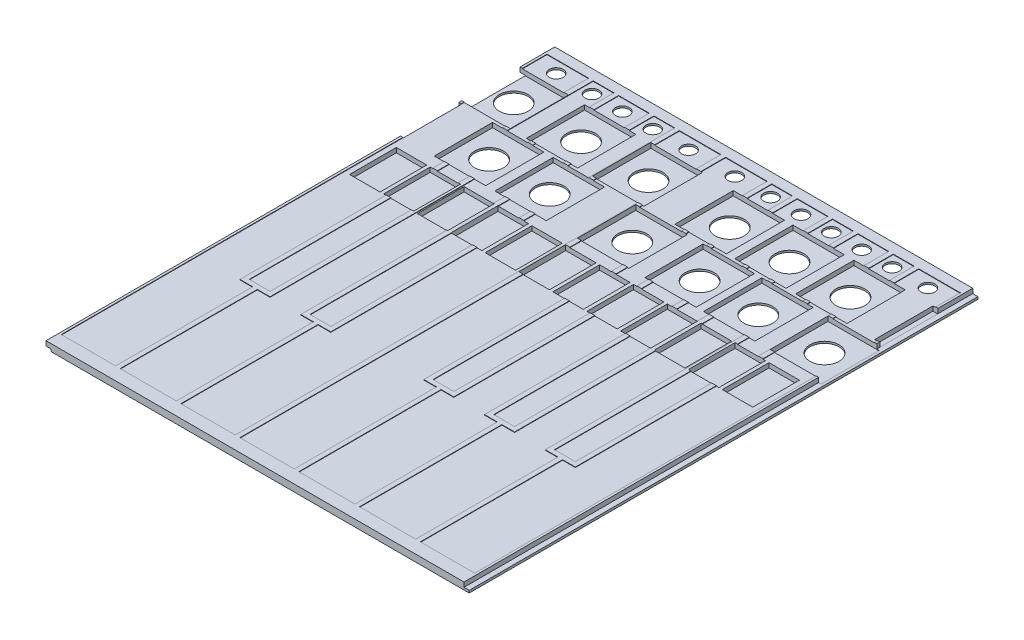
SolidWorks part; units mm, degrees
ref_plane "Plan de face" through (0, 0, 0) normal (0, 0, 1) x (1, 0, 0)
ref_plane "Plan de dessus" through (0, 0, 0) normal (0, 1, 0) x (1, 0, 0)
ref_plane "Plan de droite" through (0, 0, 0) normal (1, 0, 0) x (0, 0, -1)
sketch "Esquisse8" plane through (0, 0, 0) normal (0, 1, 0) x (1, 0, 0)
  line L1 (-19.1004, -13.1969) -> (163.8996, -13.1969)
  line L2 (-19.1004, -13.1969) -> (-19.1004, 206.8031)
  line L3 (-19.1004, 206.8031) -> (163.8996, 206.8031)
  line L4 (163.8996, -13.1969) -> (163.8996, 206.8031)
  dimension "D1" = 183
  dimension "D2" = 220
extrude "Boss.-Extru.2" add sketch "Esquisse8" along normal blind 3 contours L3 L4 L1 L2
sketch "Esquisse12" plane through (0, 3, 0) normal (0, 1, 0) x (1, 0, 0)
  line L0 (163.8996, -13.1969) -> (-19.1004, 206.8031) construction
  line L1 (72.3996, 96.8031) -> (72.0963, 96.8031) construction
  line L2 (12.8796, 130.4409) -> (12.8796, 202.4209)
  line L3 (7.3796, -7.5791) -> (31.6496, -7.5791)
  line L4 (7.3796, 51.6948) -> (12.8796, 51.6948)
  line L5 (7.3796, -7.5791) -> (7.3796, 51.6948)
  line L6 (26.1496, 130.2607) -> (26.1496, 52.2574)
  line L7 (26.1496, 52.2574) -> (26.1496, 51.6948)
  line L8 (26.1496, 51.6948) -> (31.6496, 51.6948)
  line L9 (31.6496, 51.6948) -> (31.6496, -7.5791)
  line L10 (12.8796, 51.6948) -> (12.8796, 130.4409)
  line L11 (12.8796, 202.4209) -> (26.1496, 202.4209)
  line L12 (26.1496, 202.4209) -> (26.1496, 130.2607)
  line L13 (-18.1004, 130.4209) -> (-18.1004, -7.5791)
  line L14 (-18.1004, -7.5791) -> (5.3796, -7.5791)
  line L15 (-0.1204, 130.2607) -> (-0.1204, 52.2574)
  line L16 (-0.1204, 52.2574) -> (-0.1204, 51.6948)
  line L17 (-0.1204, 51.6948) -> (5.3796, 51.6948)
  line L18 (5.3796, 51.6948) -> (5.3796, -7.5791)
  line L19 (1.8796, 131.312) -> (1.8796, 202.4209)
  line L20 (1.8796, 202.4209) -> (10.8796, 202.4209)
  line L21 (10.8796, 202.4209) -> (10.8796, 131.4176)
  line L22 (1.8796, 131.312) -> (1.8796, 53.6948)
  line L23 (1.8796, 53.6948) -> (10.8796, 53.6948)
  line L24 (10.8796, 131.4176) -> (10.8796, 53.6948)
  line L25 (-18.1004, 130.4209) -> (-18.1004, 202.4209)
  line L26 (-18.1004, 202.4209) -> (-0.1204, 202.4209)
  line L27 (-0.1204, 202.4209) -> (-0.1204, 130.2607)
  line L28 (28.1496, 130.2506) -> (28.1496, 202.4209)
  line L29 (28.1496, 202.4209) -> (37.1496, 202.4209)
  line L30 (37.1496, 202.4209) -> (37.1496, 131.4376)
  line L31 (28.1496, 130.2506) -> (28.1496, 53.6948)
  line L32 (28.1496, 53.6948) -> (37.1496, 53.6948)
  line L33 (37.1496, 131.4376) -> (37.1496, 53.6948)
  line L34 (26.1496, 202.4209) -> (30.7258, 202.4209) construction
  line L35 (57.1296, -7.5791) -> (33.6496, -7.5791)
  line L36 (57.1296, 130.4209) -> (57.1296, -7.5791)
  line L37 (39.1496, 129.6999) -> (39.1496, 51.6948)
  line L38 (39.1496, 51.6948) -> (33.6496, 51.6948)
  line L39 (33.6496, 51.6948) -> (33.6496, -7.5791)
  line L40 (39.1496, 129.6999) -> (39.1496, 202.4209)
  line L41 (39.1496, 202.4209) -> (57.1296, 202.4209)
  line L42 (57.1296, 202.4209) -> (57.1296, 130.4209)
  line L43 (59.1296, 130.3659) -> (59.1296, -7.5791)
  line L44 (59.1296, -7.5791) -> (82.6096, -7.5791)
  line L45 (77.1096, 132.5052) -> (77.1096, 54.5019)
  line L46 (77.1096, 54.5019) -> (77.1096, 53.9393)
  line L47 (77.1096, 53.9393) -> (82.6096, 53.9393)
  line L48 (82.6096, 53.9393) -> (82.6096, -7.5791)
  line L49 (59.1296, 130.3659) -> (59.1296, 202.4209)
  line L50 (59.1296, 202.4209) -> (77.1096, 202.4209)
  line L51 (77.1096, 202.4209) -> (77.1096, 132.5052)
  line L52 (-18.1004, -7.5791) -> (-18.1004, -9.5791) construction
  line L53 (-18.1004, 202.4209) -> (-18.1004, 204.4209) construction
  line L54 (-18.1004, 204.4209) -> (128.6652, 204.4209) construction
  line L55 (79.1096, 132.5152) -> (79.1096, 202.4209)
  line L56 (79.1096, 202.4209) -> (88.1096, 202.4209)
  line L57 (88.1096, 202.4209) -> (88.1096, 133.5019)
  line L58 (79.1096, 132.5152) -> (79.1096, 55.9393)
  line L59 (79.1096, 55.9393) -> (88.1096, 55.9393)
  line L60 (88.1096, 133.5019) -> (88.1096, 55.9393)
  line L61 (90.1096, 132.0831) -> (90.1096, 202.4209)
  line L62 (84.6096, -7.5791) -> (108.8796, -7.5791)
  line L63 (84.6096, 53.9393) -> (90.1096, 53.9393)
  line L64 (84.6096, -7.5791) -> (84.6096, 53.9393)
  line L65 (103.3796, 132.5052) -> (103.3796, 54.5019)
  line L66 (103.3796, 54.5019) -> (103.3796, 53.9393)
  line L67 (103.3796, 53.9393) -> (108.8796, 53.9393)
  line L68 (108.8796, 53.9393) -> (108.8796, -7.5791)
  line L69 (90.1096, 53.9393) -> (90.1096, 132.0831)
  line L70 (90.1096, 202.4209) -> (103.3796, 202.4209)
  line L71 (103.3796, 202.4209) -> (103.3796, 132.5052)
  line L72 (105.3796, 132.1219) -> (105.3796, 202.4209)
  line L73 (105.3796, 202.4209) -> (114.3796, 202.4209)
  line L74 (114.3796, 202.4209) -> (114.3796, 132.633)
  line L75 (105.3796, 132.1219) -> (105.3796, 55.9393)
  line L76 (105.3796, 55.9393) -> (114.3796, 55.9393)
  line L77 (114.3796, 132.633) -> (114.3796, 55.9393)
  line L78 (116.3796, 132.5052) -> (116.3796, 202.4209)
  line L79 (110.8796, -7.5791) -> (135.1496, -7.5791)
  line L80 (110.8796, 53.9393) -> (116.3796, 53.9393)
  line L81 (110.8796, -7.5791) -> (110.8796, 53.9393)
  line L82 (129.6496, 132.5052) -> (129.6496, 54.5019)
  line L83 (129.6496, 54.5019) -> (129.6496, 53.9393)
  line L84 (129.6496, 53.9393) -> (135.1496, 53.9393)
  line L85 (135.1496, 53.9393) -> (135.1496, -7.5791)
  line L86 (116.3796, 53.9393) -> (116.3796, 132.5052)
  line L87 (116.3796, 202.4209) -> (129.6496, 202.4209)
  line L88 (129.6496, 202.4209) -> (129.6496, 132.5052)
  line L89 (131.6496, 133.2845) -> (131.6496, 202.4209)
  line L90 (131.6496, 202.4209) -> (140.6496, 202.4209)
  line L91 (140.6496, 202.4209) -> (140.6496, 133.5019)
  line L92 (131.6496, 133.2845) -> (131.6496, 55.9393)
  line L93 (131.6496, 55.9393) -> (140.6496, 55.9393)
  line L94 (140.6496, 133.5019) -> (140.6496, 55.9393)
  line L95 (160.6296, -7.5791) -> (137.1496, -7.5791)
  line L96 (160.6296, 130.4209) -> (160.6296, -7.5791)
  line L97 (142.6496, 131.9444) -> (142.6496, 53.9393)
  line L98 (142.6496, 53.9393) -> (137.1496, 53.9393)
  line L99 (137.1496, 53.9393) -> (137.1496, -7.5791)
  line L100 (142.6496, 131.9444) -> (142.6496, 202.4209)
  line L101 (142.6496, 202.4209) -> (160.6296, 202.4209)
  line L102 (160.6296, 202.4209) -> (160.6296, 130.4209)
  line L103 (5.3796, 51.6948) -> (7.3796, 51.6948) construction
  line L104 (-0.1204, 53.129) -> (12.8796, 53.129) construction
  line L105 (-19.1004, -13.1969) -> (-19.1004, 206.8031) construction
  point P56 (68.1196, 202.4209)
  dimension "D4" = 2
  dimension "D5" = 2
  dimension "D6" = 2
  dimension "D7" = 2
  dimension "D8" = 2
  dimension "D9" = 2
  dimension "D10" = 2
  dimension "D11" = 2
  dimension "D12" = 2
  dimension "D13" = 2
  dimension "D14" = 2
  dimension "D15" = 2
  dimension "D16" = 2
  dimension "D17" = 2
  dimension "D18" = 2
  dimension "D19" = 2
  dimension "D20" = 2
  dimension "D21" = 2
  dimension "D22" = 2
  dimension "D23" = 2
  dimension "D24" = 2
  dimension "D25" = 2
  dimension "D26" = 2
  dimension "D27" = 2
  dimension "D28" = 2
  dimension "D29" = 2
  dimension "D30" = 2
  dimension "D31" = 5.5
  dimension "D32" = 2
  dimension "D33" = 5.5
  dimension "D34" = 5.5
  dimension "D35" = 5.5
  dimension "D36" = 5.5
  dimension "D37" = 5.5
  dimension "D38" = 5.5
  dimension "D39" = 5.5
  dimension "D40" = 2
  dimension "D41" = 2
  dimension "D42" = 2
  dimension "D43" = 5.5
  dimension "D44" = 5.5
  dimension "D45" = 2
  dimension "D46" = 2
  dimension "D47" = 2
  dimension "D48" = 2
  dimension "D49" = 2
  dimension "D50" = 210
  dimension "D51" = 210
  dimension "D52" = 210
  dimension "D53" = 210
  dimension "D54" = 210
  dimension "D55" = 210
  dimension "D56" = 210
  dimension "D57" = 17.98
  dimension "D58" = 13.27
  dimension "D59" = 13.27
  dimension "D60" = 17.98
  dimension "D61" = 17.98
  dimension "D62" = 13.27
  dimension "D63" = 17.98
  dimension "D64" = 2
  dimension "D65" = 2
  dimension "D66" = 1
extrude "Enlèv. mat.-Extru.8" cut sketch "Esquisse12" against normal blind 0.2
sketch "Esquisse14" plane through (0, 2.8, 0) normal (0, 1, 0) x (1, 0, 0)
  line L0 (-9.1104, 202.4209) -> (-9.1104, 197.4209) construction
  line L1 (-0.1204, 202.4209) -> (-18.1004, 202.4209) construction
  line L2 (-9.1104, 197.4209) -> (162.3729, 197.4209) construction
  line L3 (6.3796, 202.4209) -> (6.3796, 197.4209) construction
  line L4 (10.8796, 202.4209) -> (1.8796, 202.4209) construction
  line L5 (19.5146, 202.4209) -> (19.5146, 197.4209) construction
  line L6 (26.1496, 202.4209) -> (12.8796, 202.4209) construction
  line L7 (32.6496, 202.4209) -> (32.6496, 197.4209) construction
  line L8 (37.1496, 202.4209) -> (28.1496, 202.4209) construction
  line L9 (48.1396, 202.4209) -> (48.1396, 197.4209) construction
  line L10 (57.1296, 202.4209) -> (39.1496, 202.4209) construction
  line L11 (68.1196, 202.4209) -> (68.1196, 197.4209) construction
  line L12 (77.1096, 202.4209) -> (59.1296, 202.4209) construction
  line L13 (83.6096, 202.4209) -> (83.6096, 197.4209) construction
  line L14 (88.1096, 202.4209) -> (79.1096, 202.4209) construction
  line L15 (96.7446, 202.4209) -> (96.7446, 197.4209) construction
  line L16 (103.3796, 202.4209) -> (90.1096, 202.4209) construction
  line L17 (109.8796, 202.4209) -> (109.8796, 197.4209) construction
  line L18 (114.3796, 202.4209) -> (105.3796, 202.4209) construction
  line L19 (123.0146, 202.4209) -> (123.0146, 197.4209) construction
  line L20 (129.6496, 202.4209) -> (116.3796, 202.4209) construction
  line L21 (136.1496, 202.4209) -> (136.1496, 197.4209) construction
  line L22 (140.6496, 202.4209) -> (131.6496, 202.4209) construction
  line L23 (151.6396, 202.4209) -> (151.6396, 197.4209) construction
  line L24 (160.6296, 202.4209) -> (142.6496, 202.4209) construction
  circle A0 centre (-9.1104, 197.4209) radius 3
  circle A1 centre (6.3796, 197.4209) radius 3
  circle A2 centre (19.5146, 197.4209) radius 3
  circle A3 centre (32.6496, 197.4209) radius 3
  circle A4 centre (48.1396, 197.4209) radius 3
  circle A5 centre (68.1196, 197.4209) radius 3
  circle A6 centre (83.6096, 197.4209) radius 3
  circle A7 centre (96.7446, 197.4209) radius 3
  circle A8 centre (109.8796, 197.4209) radius 3
  circle A9 centre (123.0146, 197.4209) radius 3
  circle A10 centre (136.1496, 197.4209) radius 3
  circle A11 centre (151.6396, 197.4209) radius 3
extrude "Enlèv. mat.-Extru.9" cut sketch "Esquisse14" against normal blind 10
sketch "Esquisse15" plane through (0, 2.8, 0) normal (0, 1, 0) x (1, 0, 0)
  line L0 (-19.1004, 206.8031) -> (163.8996, 206.8031) construction
  line L6 (-4.5051, 165.3031) -> (17.6949, 165.3031)
  line L7 (-20.341, 191.8031) -> (1.859, 191.8031)
  line L8 (-20.341, 191.8031) -> (-20.341, 166.6031)
  line L9 (-20.341, 166.6031) -> (1.859, 166.6031)
  line L10 (1.859, 191.8031) -> (1.859, 166.6031)
  line L11 (-4.5051, 165.3031) -> (-4.5051, 140.1031)
  line L12 (-4.5051, 140.1031) -> (17.6949, 140.1031)
  line L13 (17.6949, 165.3031) -> (17.6949, 140.1031)
  line L14 (8.7728, 191.8031) -> (30.9728, 191.8031)
  line L15 (8.7728, 191.8031) -> (8.7728, 166.6031)
  line L16 (8.7728, 166.6031) -> (30.9728, 166.6031)
  line L17 (30.9728, 191.8031) -> (30.9728, 166.6031)
  line L18 (21.6997, 165.3031) -> (43.8997, 165.3031)
  line L19 (21.6997, 165.3031) -> (21.6997, 140.1031)
  line L20 (21.6997, 140.1031) -> (43.8997, 140.1031)
  line L21 (43.8997, 165.3031) -> (43.8997, 140.1031)
  line L22 (37.4261, 191.8031) -> (59.6261, 191.8031)
  line L23 (37.4261, 191.8031) -> (37.4261, 166.6031)
  line L24 (37.4261, 166.6031) -> (59.6261, 166.6031)
  line L25 (59.6261, 191.8031) -> (59.6261, 166.6031)
  line L26 (57.4227, 165.3031) -> (79.6227, 165.3031)
  line L27 (57.4227, 165.3031) -> (57.4227, 140.1031)
  line L28 (57.4227, 140.1031) -> (79.6227, 140.1031)
  line L29 (79.6227, 165.3031) -> (79.6227, 140.1031)
  line L30 (73.063, 191.8031) -> (95.263, 191.8031)
  line L31 (73.063, 191.8031) -> (73.063, 166.6031)
  line L32 (73.063, 166.6031) -> (95.263, 166.6031)
  line L33 (95.263, 191.8031) -> (95.263, 166.6031)
  line L34 (86.5318, 165.3031) -> (108.7318, 165.3031)
  line L35 (86.5318, 165.3031) -> (86.5318, 140.1031)
  line L36 (86.5318, 140.1031) -> (108.7318, 140.1031)
  line L37 (108.7318, 165.3031) -> (108.7318, 140.1031)
  line L38 (98.8805, 191.8031) -> (121.0805, 191.8031)
  line L39 (98.8805, 191.8031) -> (98.8805, 166.6031)
  line L40 (98.8805, 166.6031) -> (121.0805, 166.6031)
  line L41 (121.0805, 191.8031) -> (121.0805, 166.6031)
  line L42 (111.9109, 165.3031) -> (134.1109, 165.3031)
  line L43 (111.9109, 165.3031) -> (111.9109, 140.1031)
  line L44 (111.9109, 140.1031) -> (134.1109, 140.1031)
  line L45 (134.1109, 165.3031) -> (134.1109, 140.1031)
  line L46 (125.2379, 191.8031) -> (147.4379, 191.8031)
  line L47 (125.2379, 191.8031) -> (125.2379, 166.6031)
  line L48 (125.2379, 166.6031) -> (147.4379, 166.6031)
  line L49 (147.4379, 191.8031) -> (147.4379, 166.6031)
  line L50 (140.5398, 165.3031) -> (162.7398, 165.3031)
  line L51 (140.5398, 165.3031) -> (140.5398, 140.1031)
  line L52 (140.5398, 140.1031) -> (162.7398, 140.1031)
  line L53 (162.7398, 165.3031) -> (162.7398, 140.1031)
  line L54 (-19.1004, 191.8031) -> (190.2079, 191.8031) construction
  line L55 (-19.1004, -13.1969) -> (-19.1004, 206.8031) construction
  line L56 (-19.1004, 165.5149) -> (203.3844, 166.3385) construction
  dimension "D1" = 15
  dimension "D2" = 15
  dimension "D3" = 22.2
  dimension "D4" = 25.2
  dimension "D5" = 15
  dimension "D6" = 15
  dimension "D7" = 15
  dimension "D8" = 15
  dimension "D9" = 15
  dimension "D10" = 0.212
  dimension "D11" = 41.5
  dimension "D12" = 41.5
  dimension "D13" = 41.5
  dimension "D14" = 41.5
  dimension "D15" = 41.5
  dimension "D16" = 41.5
  dimension "D17" = 25.2
  dimension "D18" = 25.2
  dimension "D19" = 25.2
  dimension "D20" = 25.2
  dimension "D21" = 25.2
  dimension "D22" = 22.2
  dimension "D23" = 22.2
  dimension "D24" = 22.2
  dimension "D25" = 22.2
  dimension "D26" = 22.2
  dimension "D27" = 22.2
  dimension "D28" = 22.2
  dimension "D29" = 22.2
  dimension "D30" = 22.2
  dimension "D31" = 22.2
  dimension "D32" = 22.2
  dimension "D33" = 25.2
  dimension "D34" = 25.2
  dimension "D35" = 25.2
  dimension "D36" = 25.2
  dimension "D37" = 25.2
  dimension "D38" = 25.2
extrude "Enlèv. mat.-Extru.10" cut sketch "Esquisse15" against normal blind 2 and the other way blind 2
sketch "Esquisse16" plane through (0, 0.8, 0) normal (0, 1, 0) x (1, 0, 0)
  line L0 (-20.341, 191.8031) -> (1.859, 166.6031) construction
  line L1 (-4.5051, 165.3031) -> (17.6949, 140.1031) construction
  line L2 (8.7728, 166.6031) -> (30.9728, 191.8031) construction
  line L3 (43.8997, 165.3031) -> (21.6997, 140.1031) construction
  line L5 (57.4227, 140.1031) -> (79.6227, 165.3031) construction
  line L6 (1.859, 191.8031) -> (-20.341, 191.8031) construction
  line L7 (73.063, 191.8031) -> (95.263, 166.6031) construction
  line L8 (98.8805, 191.8031) -> (121.0805, 166.6031) construction
  line L9 (86.5318, 165.3031) -> (108.7318, 140.1031) construction
  line L10 (125.2379, 191.8031) -> (147.4379, 166.6031) construction
  line L11 (111.9109, 165.3031) -> (134.1109, 140.1031) construction
  line L12 (140.5398, 165.3031) -> (162.7398, 140.1031) construction
  circle A1 centre (19.8728, 179.2031) radius 6.25
  circle A2 centre (49.0329, 179.2031) radius 6.25
  circle A3 centre (84.163, 179.2031) radius 6.25
  circle A4 centre (109.9805, 179.2031) radius 6.25
  circle A5 centre (136.3379, 179.2031) radius 6.25
  circle A6 centre (6.5949, 152.7031) radius 6.25
  circle A7 centre (32.7997, 152.7031) radius 6.25
  circle A8 centre (68.5227, 152.7031) radius 6.25
  circle A9 centre (97.6318, 152.7031) radius 6.25
  circle A10 centre (123.0109, 152.7031) radius 6.25
  circle A11 centre (151.6398, 152.7031) radius 6.25
  circle A12 centre (-9.241, 179.2031) radius 6.25
extrude "Enlèv. mat.-Extru.11" cut sketch "Esquisse16" against normal blind 2 contours A1 | A6 | A7 | A2 | A8 | A3 | A9 | A4 | A10 | A5 | A11 | A12 region at (19.8728, 0.8, -179.2031) region at (49.0329, 0.8, -179.2031) region at (84.163, 0.8, -179.2031) region at (109.9805, 0.8, -179.2031) region at (136.3379, 0.8, -179.2031) region at (6.5949, 0.8, -152.7031) region at (32.7997, 0.8, -152.7031) region at (68.5227, 0.8, -152.7031) region at (97.6318, 0.8, -152.7031) region at (123.0109, 0.8, -152.7031) region at (151.6398, 0.8, -152.7031)
sketch "Esquisse21" plane through (0, 0, 0) normal (0, -1, 0) x (-1, 0, 0)
  line L1 (14.1104, 192.4209) -> (4.1104, 192.4209)
  line L2 (14.1104, 192.4209) -> (14.1104, 202.4209)
  line L3 (14.1104, 202.4209) -> (4.1104, 202.4209)
  line L4 (4.1104, 192.4209) -> (4.1104, 202.4209)
  line L5 (14.1104, 192.4209) -> (4.1104, 202.4209) construction
  line L6 (14.1104, 202.4209) -> (4.1104, 192.4209) construction
  line L7 (-1.3796, 192.4209) -> (-11.3796, 192.4209)
  line L8 (-1.3796, 192.4209) -> (-1.3796, 202.4209)
  line L9 (-1.3796, 202.4209) -> (-11.3796, 202.4209)
  line L10 (-11.3796, 192.4209) -> (-11.3796, 202.4209)
  line L11 (-1.3796, 192.4209) -> (-11.3796, 202.4209) construction
  line L12 (-1.3796, 202.4209) -> (-11.3796, 192.4209) construction
  line L13 (-14.5146, 192.4209) -> (-24.5146, 192.4209)
  line L14 (-14.5146, 192.4209) -> (-14.5146, 202.4209)
  line L15 (-14.5146, 202.4209) -> (-24.5146, 202.4209)
  line L16 (-24.5146, 192.4209) -> (-24.5146, 202.4209)
  line L17 (-14.5146, 192.4209) -> (-24.5146, 202.4209) construction
  line L18 (-14.5146, 202.4209) -> (-24.5146, 192.4209) construction
  line L19 (-27.6496, 192.4209) -> (-37.6496, 192.4209)
  line L20 (-27.6496, 192.4209) -> (-27.6496, 202.4209)
  line L21 (-27.6496, 202.4209) -> (-37.6496, 202.4209)
  line L22 (-37.6496, 192.4209) -> (-37.6496, 202.4209)
  line L23 (-27.6496, 192.4209) -> (-37.6496, 202.4209) construction
  line L24 (-27.6496, 202.4209) -> (-37.6496, 192.4209) construction
  line L25 (-43.1396, 192.4209) -> (-53.1396, 192.4209)
  line L26 (-43.1396, 192.4209) -> (-43.1396, 202.4209)
  line L27 (-43.1396, 202.4209) -> (-53.1396, 202.4209)
  line L28 (-53.1396, 192.4209) -> (-53.1396, 202.4209)
  line L29 (-43.1396, 192.4209) -> (-53.1396, 202.4209) construction
  line L30 (-43.1396, 202.4209) -> (-53.1396, 192.4209) construction
  line L31 (-63.1196, 192.4209) -> (-73.1196, 192.4209)
  line L32 (-63.1196, 192.4209) -> (-63.1196, 202.4209)
  line L33 (-63.1196, 202.4209) -> (-73.1196, 202.4209)
  line L34 (-73.1196, 192.4209) -> (-73.1196, 202.4209)
  line L35 (-63.1196, 192.4209) -> (-73.1196, 202.4209) construction
  line L36 (-63.1196, 202.4209) -> (-73.1196, 192.4209) construction
  line L37 (-78.6096, 192.4209) -> (-88.6096, 192.4209)
  line L38 (-78.6096, 192.4209) -> (-78.6096, 202.4209)
  line L39 (-78.6096, 202.4209) -> (-88.6096, 202.4209)
  line L40 (-88.6096, 192.4209) -> (-88.6096, 202.4209)
  line L41 (-78.6096, 192.4209) -> (-88.6096, 202.4209) construction
  line L42 (-78.6096, 202.4209) -> (-88.6096, 192.4209) construction
  line L43 (-91.7446, 192.4209) -> (-101.7446, 192.4209)
  line L44 (-91.7446, 192.4209) -> (-91.7446, 202.4209)
  line L45 (-91.7446, 202.4209) -> (-101.7446, 202.4209)
  line L46 (-101.7446, 192.4209) -> (-101.7446, 202.4209)
  line L47 (-91.7446, 192.4209) -> (-101.7446, 202.4209) construction
  line L48 (-91.7446, 202.4209) -> (-101.7446, 192.4209) construction
  line L49 (-104.8796, 192.4209) -> (-114.8796, 192.4209)
  line L50 (-104.8796, 192.4209) -> (-104.8796, 202.4209)
  line L51 (-104.8796, 202.4209) -> (-114.8796, 202.4209)
  line L52 (-114.8796, 192.4209) -> (-114.8796, 202.4209)
  line L53 (-104.8796, 192.4209) -> (-114.8796, 202.4209) construction
  line L54 (-104.8796, 202.4209) -> (-114.8796, 192.4209) construction
  line L55 (-118.0146, 192.4209) -> (-128.0146, 192.4209)
  line L56 (-118.0146, 192.4209) -> (-118.0146, 202.4209)
  line L57 (-118.0146, 202.4209) -> (-128.0146, 202.4209)
  line L58 (-128.0146, 192.4209) -> (-128.0146, 202.4209)
  line L59 (-118.0146, 192.4209) -> (-128.0146, 202.4209) construction
  line L60 (-118.0146, 202.4209) -> (-128.0146, 192.4209) construction
  line L61 (-131.1496, 192.4209) -> (-141.1496, 192.4209)
  line L62 (-131.1496, 192.4209) -> (-131.1496, 202.4209)
  line L63 (-131.1496, 202.4209) -> (-141.1496, 202.4209)
  line L64 (-141.1496, 192.4209) -> (-141.1496, 202.4209)
  line L65 (-131.1496, 192.4209) -> (-141.1496, 202.4209) construction
  line L66 (-131.1496, 202.4209) -> (-141.1496, 192.4209) construction
  line L67 (-146.6396, 192.4209) -> (-156.6396, 192.4209)
  line L68 (-146.6396, 192.4209) -> (-146.6396, 202.4209)
  line L69 (-146.6396, 202.4209) -> (-156.6396, 202.4209)
  line L70 (-156.6396, 192.4209) -> (-156.6396, 202.4209)
  line L71 (-146.6396, 192.4209) -> (-156.6396, 202.4209) construction
  line L72 (-146.6396, 202.4209) -> (-156.6396, 192.4209) construction
  point P0 (9.1104, 197.4209)
  point P6 (-6.3796, 197.4209)
  point P12 (-19.5146, 197.4209)
  point P18 (-32.6496, 197.4209)
  point P24 (-48.1396, 197.4209)
  point P30 (-68.1196, 197.4209)
  point P36 (-83.6096, 197.4209)
  point P42 (-96.7446, 197.4209)
  point P48 (-109.8796, 197.4209)
  point P54 (-123.0146, 197.4209)
  point P60 (-136.1496, 197.4209)
  point P66 (-151.6396, 197.4209)
extrude "Enlèv. mat.-Extru.16" cut sketch "Esquisse21" against normal blind 2
sketch "Esquisse22" plane through (0, 3, 0) normal (0, 1, 0) x (1, 0, 0)
  line L0 (160.6296, 200.1746) -> (156.3183, 200.1746) construction
  line L1 (160.6296, 165.3031) -> (160.6296, 202.4209) construction
  line L2 (-19.1004, 206.8031) -> (163.8996, 206.8031) construction
  line L3 (161.6296, 206.8031) -> (163.8996, 206.8031)
  line L4 (161.6296, 206.8031) -> (161.6296, -13.1969)
  line L5 (161.6296, -13.1969) -> (163.8996, -13.1969)
  line L6 (163.8996, 206.8031) -> (163.8996, -13.1969)
  dimension "D1" = 1
extrude "Enlèv. mat.-Extru.17" cut sketch "Esquisse22" against normal blind 2 contours L4 L5 L6 L3
sketch "Esquisse24" plane through (0, 0.8, 0) normal (0, 1, 0) x (1, 0, 0)
  line L1 (162.7398, 165.3031) -> (161.6296, 165.3031)
  line L2 (162.7398, 165.3031) -> (162.7398, 140.1031)
  line L3 (162.7398, 140.1031) -> (161.6296, 140.1031)
  line L4 (161.6296, 165.3031) -> (161.6296, 140.1031)
  line L5 (-19.1004, 209.6913) -> (161.6296, 209.6913) construction
  line L7 (71.2646, 206.8031) -> (70.2646, 206.8031) construction
  line L9 (-19.1004, 206.8031) -> (161.6296, 206.8031) construction
  line L10 (71.2646, 206.8031) -> (71.8197, 206.8031) construction
  line L11 (71.8197, 206.8031) -> (71.8197, -69.8958) construction
  line L12 (-19.1003, 140.1031) -> (-17.9902, 140.1031)
  line L13 (-17.9902, 165.3031) -> (-17.9902, 140.1031)
  line L14 (-19.1003, 165.3031) -> (-17.9902, 165.3031)
  line L15 (-19.1003, 165.3031) -> (-19.1003, 140.1031)
extrude "Enlèv. mat.-Extru.18" cut sketch "Esquisse24" against normal blind 1 and the other way blind 8 contours L14 L13 L12 L15
sketch "Esquisse25" plane through (-17.9902, 0, 0) normal (-1, 0, 0) x (0, 0, 1)
  line L0 (-140.1031, 2.8) -> (-140.1031, 0) construction
  line L1 (-165.3031, 0) -> (-140.1031, 0)
  line L2 (-165.3031, 0) -> (-165.3031, 0.8)
  line L3 (-165.3031, 0.8) -> (-140.1031, 0.8)
  line L4 (-140.1031, 0) -> (-140.1031, 0.8)
  line L5 (-166.6031, 0.8) -> (-191.8031, 0.8) construction
  line L6 (-165.3031, 0) -> (-206.8031, 0) construction
  dimension "D1" = 0.8
  dimension "D2" = 0.8
extrude "Boss.-Extru.3" add sketch "Esquisse25" along normal blind 1.11 contours L3 L4 L1 L2
sketch "Esquisse26" plane through (0, 2.8, 0) normal (0, 1, 0) x (1, 0, 0)
  line L0 (161.6296, 206.8031) -> (161.6296, 165.3031) construction
  line L1 (159.4296, 191.8031) -> (161.6296, 191.8031)
  line L2 (159.4296, 191.8031) -> (159.4296, 166.6031)
  line L3 (159.4296, 166.6031) -> (161.6296, 166.6031)
  line L4 (161.6296, 191.8031) -> (161.6296, 166.6031)
  line L6 (-19.1004, 206.8031) -> (161.6296, 206.8031) construction
  dimension "D1" = 2.2
  dimension "D2" = 25.2
  dimension "D3" = 15
extrude "Enlèv. mat.-Extru.19" cut sketch "Esquisse26" against normal blind 2 and the other way blind 2
sketch "Esquisse27" plane through (0, 2.8, 0) normal (0, 1, 0) x (1, 0, 0)
  line L0 (-19.1003, 140.1031) -> (163.8996, 140.1031) construction
  line L1 (163.8996, 206.8031) -> (163.8996, -13.1969) construction
  line L2 (-1.2716, 135.1031) -> (11.8784, 135.1031)
  line L3 (-15.9216, 135.1031) -> (-2.7716, 135.1031)
  line L4 (-15.9216, 135.1031) -> (-15.9216, 114.9031)
  line L5 (-15.9216, 114.9031) -> (-2.7716, 114.9031)
  line L6 (-2.7716, 135.1031) -> (-2.7716, 114.9031)
  line L7 (-1.2716, 135.1031) -> (-1.2716, 114.9031)
  line L8 (-1.2716, 114.9031) -> (11.8784, 114.9031)
  line L9 (11.8784, 135.1031) -> (11.8784, 114.9031)
  line L10 (-9.5142, 10.1) -> (3.6358, 10.1)
  line L11 (-9.5142, 10.1) -> (-9.5142, -10.1)
  line L12 (-9.5142, -10.1) -> (3.6358, -10.1)
  line L13 (3.6358, 10.1) -> (3.6358, -10.1)
  line L14 (-2.9392, 10.1) -> (10.2108, 10.1)
  line L15 (-2.9392, 10.1) -> (-2.9392, -10.1)
  line L16 (-2.9392, -10.1) -> (10.2108, -10.1)
  line L17 (10.2108, 10.1) -> (10.2108, -10.1)
  line L22 (-8.1813, -52.5449) -> (4.9687, -52.5449)
  line L23 (-8.1813, -52.5449) -> (-8.1813, -72.7449)
  line L24 (-8.1813, -72.7449) -> (4.9687, -72.7449)
  line L25 (4.9687, -52.5449) -> (4.9687, -72.7449)
  line L26 (13.3784, 135.1031) -> (26.5284, 135.1031)
  line L27 (13.3784, 135.1031) -> (13.3784, 114.9031)
  line L28 (13.3784, 114.9031) -> (26.5284, 114.9031)
  line L29 (26.5284, 135.1031) -> (26.5284, 114.9031)
  line L30 (28.0284, 135.1465) -> (41.1784, 135.1465)
  line L31 (28.0284, 135.1465) -> (28.0284, 114.9465)
  line L32 (28.0284, 114.9465) -> (41.1784, 114.9465)
  line L33 (41.1784, 135.1465) -> (41.1784, 114.9465)
  line L34 (18.9541, 10.1) -> (32.1041, 10.1)
  line L35 (18.9541, 10.1) -> (18.9541, -10.1)
  line L36 (18.9541, -10.1) -> (32.1041, -10.1)
  line L37 (32.1041, 10.1) -> (32.1041, -10.1)
  line L38 (42.6784, 135.1031) -> (55.8284, 135.1031)
  line L39 (42.6784, 135.1031) -> (42.6784, 114.9031)
  line L40 (42.6784, 114.9031) -> (55.8284, 114.9031)
  line L41 (55.8284, 135.1031) -> (55.8284, 114.9031)
  line L42 (49.2879, 10.1) -> (62.4379, 10.1)
  line L43 (49.2879, 10.1) -> (49.2879, -10.1)
  line L44 (49.2879, -10.1) -> (62.4379, -10.1)
  line L45 (62.4379, 10.1) -> (62.4379, -10.1)
  line L46 (57.3284, 135.1031) -> (70.4784, 135.1031)
  line L47 (57.3284, 135.1031) -> (57.3284, 114.9031)
  line L48 (57.3284, 114.9031) -> (70.4784, 114.9031)
  line L49 (70.4784, 135.1031) -> (70.4784, 114.9031)
  line L50 (62.9949, 10.1) -> (76.1449, 10.1)
  line L51 (62.9949, 10.1) -> (62.9949, -10.1)
  line L52 (62.9949, -10.1) -> (76.1449, -10.1)
  line L53 (76.1449, 10.1) -> (76.1449, -10.1)
  line L54 (71.9784, 135.1031) -> (85.1284, 135.1031)
  line L55 (71.9784, 135.1031) -> (71.9784, 114.9031)
  line L56 (71.9784, 114.9031) -> (85.1284, 114.9031)
  line L57 (85.1284, 135.1031) -> (85.1284, 114.9031)
  line L58 (86.6284, 135.1031) -> (99.7784, 135.1031)
  line L59 (86.6284, 135.1031) -> (86.6284, 114.9031)
  line L60 (86.6284, 114.9031) -> (99.7784, 114.9031)
  line L61 (99.7784, 135.1031) -> (99.7784, 114.9031)
  line L62 (101.2784, 135.1031) -> (114.4284, 135.1031)
  line L63 (101.2784, 135.1031) -> (101.2784, 114.9031)
  line L64 (101.2784, 114.9031) -> (114.4284, 114.9031)
  line L65 (114.4284, 135.1031) -> (114.4284, 114.9031)
  line L66 (115.9284, 135.1031) -> (129.0784, 135.1031)
  line L67 (115.9284, 135.1031) -> (115.9284, 114.9031)
  line L68 (115.9284, 114.9031) -> (129.0784, 114.9031)
  line L69 (129.0784, 135.1031) -> (129.0784, 114.9031)
  line L70 (130.5784, 135.1031) -> (143.7284, 135.1031)
  line L71 (130.5784, 135.1031) -> (130.5784, 114.9031)
  line L72 (130.5784, 114.9031) -> (143.7284, 114.9031)
  line L73 (143.7284, 135.1031) -> (143.7284, 114.9031)
  line L74 (145.2284, 135.1031) -> (158.3784, 135.1031)
  line L75 (145.2284, 135.1031) -> (145.2284, 114.9031)
  line L76 (145.2284, 114.9031) -> (158.3784, 114.9031)
  line L77 (158.3784, 135.1031) -> (158.3784, 114.9031)
  dimension "D1" = 5
  dimension "D2" = 5
  dimension "D3" = 5
  dimension "D4" = 5
  dimension "D5" = 5
  dimension "D6" = 5
  dimension "D7" = 5
  dimension "D8" = 5
  dimension "D9" = 5
  dimension "D10" = 5
  dimension "D11" = 5
  dimension "D12" = 1.5
  dimension "D13" = 1.5
  dimension "D14" = 1.5
  dimension "D15" = 1.5
  dimension "D16" = 1.5
  dimension "D17" = 1.5
  dimension "D18" = 1.5
  dimension "D19" = 1.5
  dimension "D20" = 1.5
  dimension "D21" = 1.5
  dimension "D22" = 1.5
extrude "Enlèv. mat.-Extru.20" cut sketch "Esquisse27" against normal blind 2 and the other way blind 2 contours L3 L6 L5 L4 | L2 L9 L8 L7 | L26 L29 L28 L27 | L30 L33 L32 L31 | L38 L41 L40 L39 | L46 L49 L48 L47 | L54 L57 L56 L55 | L58 L61 L60 L59 | L62 L65 L64 L63 | L66 L69 L68 L67 | L70 L73 L72 L71 | L74 L77 L76 L75
sketch "Esquisse31" plane through (0, 0, 0) normal (0, -1, 0) x (-1, 0, 0)
  line L0 (19.1004, 206.8031) -> (-163.8996, 206.8031) construction
  line L1 (16.9004, -13.1969) -> (19.1004, -13.1969)
  line L2 (16.9004, -13.1969) -> (16.9004, 206.8031)
  line L3 (16.9004, 206.8031) -> (19.1004, 206.8031)
  line L4 (19.1004, -13.1969) -> (19.1004, 206.8031)
  line L5 (19.1004, 165.3031) -> (19.1004, 206.8031) construction
  line L7 (19.1004, -13.1969) -> (-163.8996, -13.1969) construction
  dimension "D1" = 2.2
  dimension "D2" = 0
  dimension "D3" = 0
extrude "Enlèv. mat.-Extru.21" cut sketch "Esquisse31" against normal blind 1
